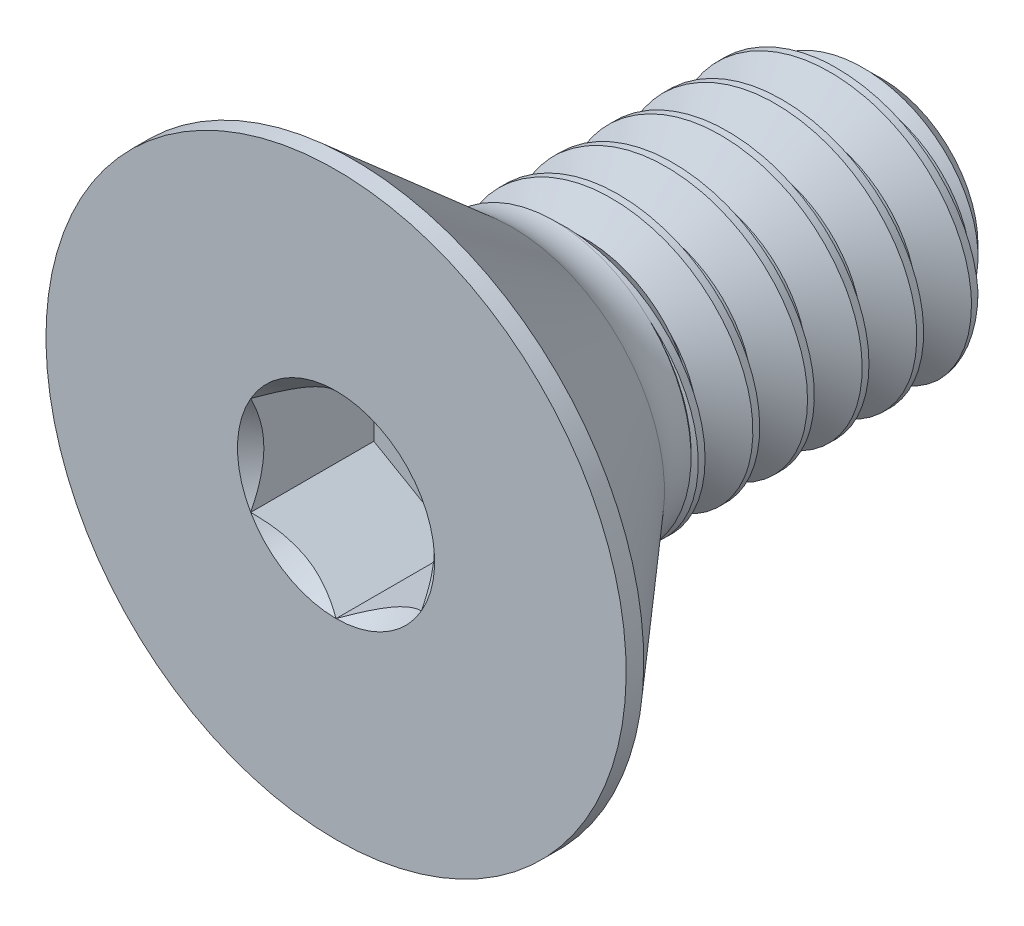
SolidWorks part; units mm, degrees
ref_plane "Front" through (0, 0, 0) normal (0, 0, 1) x (1, 0, 0)
ref_plane "Top" through (0, 0, 0) normal (0, 1, 0) x (1, 0, 0)
ref_plane "Right" through (0, 0, 0) normal (1, 0, 0) x (0, 0, -1)
sketch "Sketch1" plane through (0, 0, 0) normal (1, 0, 0) x (0, 0, -1)
  line L0 (0, 6.7437) -> (0.4089, 6.7437) construction
  line L1 (0.4089, 6.7437) -> (4.0894, 3.5443) construction
  line L2 (0, 3.175) -> (12.7, 3.175)
  line L3 (12.7, 3.175) -> (12.7, 0)
  line L4 (12.7, 0) -> (0, 0)
  line L5 (0, 0) -> (0, 6.7437) construction
  line L6 (0, 6.7437) -> (0, -6.7437) construction
  line L7 (12.7, 3.175) -> (12.7, -3.175) construction
  line L8 (0, -6.7437) -> (0.4089, -6.7437) construction
  line L9 (0.4089, -6.7437) -> (4.0894, -3.5443) construction
  line L11 (0, 3.175) -> (0, 0)
  line L12 (5.0772, 3.175) -> (5.0772, 0) construction
  arc A1 (4.0894, 3.5443) -> (5.0772, 3.175) centre (5.0772, 4.6807) ccw construction
  dimension "D1" = 0.4089
  dimension "Head Ht" = 4.0894
  dimension "Head Dia" = 13.4874
  dimension "Dia" = 6.35
  dimension "Lg" = 12.7
  dimension "Head Angle" = 82
revolve "Revolve1" add sketch "Sketch1" angle 360 about L4
sketch "Sketch3" plane through (0, 0, -12.7) normal (0, 0, -1) x (-1, 0, 0)
  circle A0 centre (0, 0) radius 3.175
curve "Helix/Spiral1" pitch 1.27 height 12.7 radius 3.175 centre (0, 0, -12.7) axis (0, 0, 1) start towards (0, 1, 0)
sketch "Sketch2" plane through (0, 0, 0) normal (1, 0, 0) x (0, 0, -1)
  line L0 (12.7, 3.175) -> (13.8113, 3.175)
  line L1 (13.8113, 3.175) -> (13.335, 2.3501)
  line L2 (13.335, 2.3501) -> (13.1762, 2.3501)
  line L3 (13.1762, 2.3501) -> (12.7, 3.175)
  line L4 (12.9381, 2.7626) -> (13.5731, 2.7626) construction
  dimension "D1" = 60
  dimension "D2" = 0.1588
  dimension "D3" = 0.635
chamfer "Chamfer1" distance 0.9525 angle 45 1 edges at (0, 3.175, -12.7)
sweep "Cut-Sweep1" cut profiles "Sketch2" path "Helix/Spiral1"
sketch "Sketch7" plane through (0, 0, 0) normal (1, 0, 0) x (0, 0, -1)
  line L0 (0, 6.7437) -> (0.4089, 6.7437) construction
  line L1 (0.4089, 6.7437) -> (4.0894, 3.5443) construction
  line L2 (0, 6.7437) -> (0.4089, 6.7437)
  line L3 (0.4089, 6.7437) -> (4.0894, 3.5443)
  line L4 (5.0772, 3.175) -> (5.0772, 0) construction
  line L5 (5.0772, 3.175) -> (5.0772, 0)
  line L7 (0, 0) -> (0, 6.7437) construction
  line L8 (0, 0) -> (0, 6.7437)
  line L9 (0, 0) -> (5.0772, 0)
  line L10 (7.4181, 0) -> (-7.4181, 0) construction
  arc A0 (4.0894, 3.5443) -> (5.0772, 3.175) centre (5.0772, 4.6807) ccw construction
  arc A1 (4.0894, 3.5443) -> (5.0772, 3.175) centre (5.0772, 4.6807) ccw
revolve "Revolve2" add sketch "Sketch7" angle 360 about L9
ref_plane "Plane1" through (0, 0, -5.0772) normal (0, 0, 1) x (1, 0, 0)
sketch "Sketch8" plane through (0, 0, -5.0772) normal (0, 0, 1) x (1, 0, 0)
  circle A0 centre (0, 0) radius 3.175
extrude "Boss-Extrude1" add sketch "Sketch8" against normal through all draft 45
sketch "Sketch11" [suppressed] plane through (0, 0, 0) normal (1, 0, 0) x (0, 0, -1)
  line L0 (4.4996, 0) -> (-4.4996, 0) construction
  line L1 (7.3025, 3.8989) -> (1.7272, 3.8989)
  line L2 (7.3025, 3.8989) -> (7.3025, -3.8989)
  line L3 (7.3025, -3.8989) -> (1.7272, -3.8989)
  line L4 (1.7272, 3.8989) -> (1.7272, -3.8989)
  line L5 (0, 3.8989) -> (0.1727, 3.8989) construction
  line L7 (4.7625, 1.7526) -> (4.7625, 0) construction
  point P4 (1.7272, 0)
  dimension "D1" = 2.54
extrude "Cut-Extrude4" [suppressed] cut sketch "Sketch11" against normal through all and the other way through all
combine bodies "Combine1" operation type add bodies to combine 117 114
sketch "Sketch5" plane through (0, 0, 0) normal (0, 0, 1) x (1, 0, 0)
  line L1 (1.9844, -1.1457) -> (1.9844, 1.1457)
  line L2 (1.9844, 1.1457) -> (0, 2.2914)
  line L3 (0, 2.2914) -> (-1.9844, 1.1457)
  line L4 (-1.9844, 1.1457) -> (-1.9844, -1.1457)
  line L5 (-1.9844, -1.1457) -> (0, -2.2914)
  line L6 (0, -2.2914) -> (1.9844, -1.1457)
  circle A0 centre (0, 0) radius 1.9844 construction
  dimension "Hex" = 3.9688
extrude "Cut-Extrude2" cut sketch "Sketch5" against normal blind 2.8626
sketch "Sketch6" plane through (0, 0, 0) normal (0, 0, 1) x (1, 0, 0)
  circle A0 centre (0, 0) radius 2.2914
extrude "Cut-Extrude3" cut sketch "Sketch6" against normal blind 2.8626 draft 45
sketch "Sketch9" [suppressed] plane through (0, 0, -5.0772) normal (0, 0, 1) x (1, 0, 0)
  circle A1 centre (0, 0) radius 3.175
  circle A2 centre (0, 0) radius 3.175
  point P0 (0, 3.175)
  dimension "D1" = 0
extrude "Boss-Extrude2" [suppressed] add sketch "Sketch9" against normal offset from surface (20.3228 mm away) 44.45 up to face at (0, 2.2225, -12.7)
sketch "Sketch10" plane through (0, 0, 0) normal (1, 0, 0) x (0, 0, -1)
  line L0 (12.7, 3.175) -> (12.7, -3.175) construction
  point P0 (10.795, -3.175)
  dimension "D1" = 1.905
equation "\"D3@Helix/Spiral1\" = \"Lg@Sketch1\""
equation "\"D2@Sketch2\" = \"D4@Helix/Spiral1\" * .125"
equation "\"D3@Sketch2\" = \"D4@Helix/Spiral1\" * .5"
equation "\"D1@Chamfer1\" = \"D4@Helix/Spiral1\" * .75"
equation "\"D1@Cut-Extrude2\" = \"Head Ht@Sketch1\" * .7"
equation "\"D1@Sketch1\" = \"Head Ht@Sketch1\" * .1"
equation "\"D1@Sketch10\" = \"D4@Helix/Spiral1\" * 1.5"
equation "\"D1@Cut-Extrude3\" = \"D1@Cut-Extrude2\""
